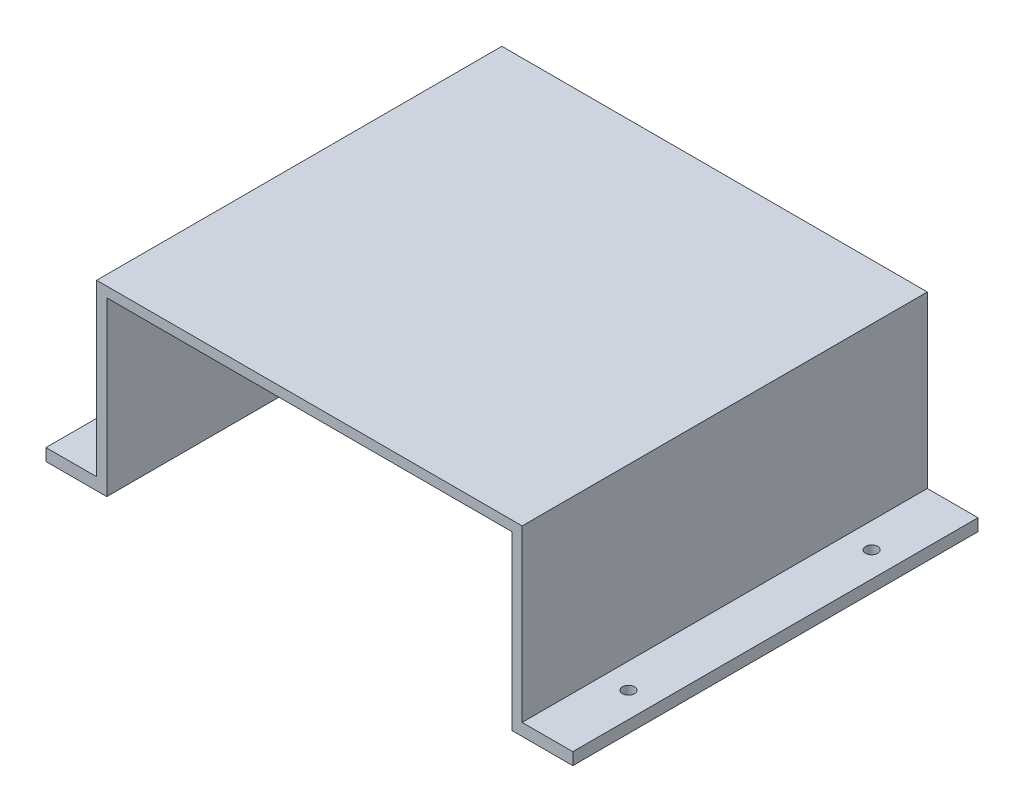
SolidWorks part; units mm, degrees
ref_plane "Front Plane" through (0, 0, 0) normal (0, 0, 1) x (1, 0, 0)
ref_plane "Top Plane" through (0, 0, 0) normal (0, 1, 0) x (1, 0, 0)
ref_plane "Right Plane" through (0, 0, 0) normal (1, 0, 0) x (0, 0, -1)
sketch "Sketch1" plane through (0, 0, 0) normal (0, 0, 1) x (1, 0, 0)
  line L1 (-67.9265, -4.0405) -> (32.0735, -4.0405)
  line L2 (-67.9265, -4.0405) -> (-67.9265, -74.0405)
  line L3 (-67.9265, -74.0405) -> (32.0735, -74.0405)
  line L4 (32.0735, -4.0405) -> (32.0735, -74.0405)
  line L5 (-70.4265, -1.5405) -> (34.5735, -1.5405)
  line L6 (-70.4265, -1.5405) -> (-70.4265, -76.5405)
  line L7 (-70.4265, -76.5405) -> (34.5735, -76.5405)
  line L8 (34.5735, -1.5405) -> (34.5735, -76.5405)
  dimension "D1" = 100
  dimension "D2" = 70
  dimension "D3" = 2.5
  dimension "D4" = 2.5
  dimension "D5" = 2.5
  dimension "D6" = 2.5
extrude "Boss-Extrude1" add sketch "Sketch1" along normal blind 100
extrude "Boss-Extrude2" add sketch "Sketch1<2>" along normal blind 3 contours L6 L7 L8 L5
sketch "Sketch1<2>" plane through (0, 0, 0) normal (0, 0, 1) x (1, 0, 0) same geometry as "Sketch1"
sketch "Sketch4" plane through (0, -1.5405, 0) normal (0, 1, 0) x (1, 0, 0)
  line L0 (-68.2059, -51.5) -> (-67.9265, -51.5)
  line L2 (-67.9265, -3) -> (32.3529, -3)
  line L3 (-67.9265, -3) -> (-67.9265, -51.5)
  line L5 (32.3529, -3) -> (32.3529, -51.5)
  arc A0 (32.3529, -51.5) -> (-68.2059, -51.5) centre (-17.9265, -51.5) ccw
extrude "Boss-Extrude3" add sketch "Sketch4" against normal blind 73 contours A0 L2 L3 | A0 L5 L2 region at (22.6295, -1.5405, 14.0826) region at (-58.2185, -1.5405, 13.7681)
sketch "Sketch5" plane through (0, -76.5405, 0) normal (0, -1, 0) x (1, 0, 0)
  line L1 (-67.9265, 100) -> (31.6349, 100)
  line L2 (-67.9265, 100) -> (-67.9265, 46.2067)
  line L3 (-31.579, 3.1096) -> (-4.2739, 3.1096)
  line L4 (31.6349, 100) -> (31.6349, 43.0327)
  arc A1 (-67.9265, 46.2067) -> (-31.1842, 3) centre (-17.9265, 51.5) ccw construction
  arc A2 (-4.6687, 3) -> (32.0735, 46.2067) centre (-17.9265, 51.5) ccw construction
  arc A3 (-67.9265, 46.2067) -> (-31.579, 3.1096) centre (-17.9265, 51.5) ccw
  arc A4 (-4.2739, 3.1096) -> (32.0735, 46.2067) centre (-17.9265, 51.5) ccw
  line M3 (34.5735, 100) -> (-70.4265, 100)
extrude "Cut-Extrude3" cut sketch "Sketch5" against normal blind 21.5 contours L3 A4 L4 L2 A3 M3 region at (-18.0648, -76.5405, 55.3892)
sketch "Sketch6" plane through (0, -76.5405, 0) normal (0, -1, 0) x (1, 0, 0)
  line L8 (-67.9265, 46.2067) -> (-67.9265, 100)
  line L9 (-67.9265, 100) -> (-70.4265, 100)
  line L10 (-70.4265, 100) -> (-70.4265, 0)
  line L11 (-70.4265, 0) -> (34.5735, 0)
  line L12 (34.5735, 0) -> (34.5735, 100)
  line L13 (34.5735, 100) -> (31.6349, 100)
  line L14 (31.6349, 100) -> (31.6349, 43.0327)
  line L15 (-4.2739, 3.1096) -> (-31.579, 3.1096)
  line L16 (-67.9265, 46.2067) -> (-67.9265, 100)
  line L17 (-67.9265, 100) -> (-70.4265, 100)
  line L18 (-70.4265, 100) -> (-70.4265, 0)
  line L19 (-70.4265, 0) -> (34.5735, 0)
  line L20 (34.5735, 0) -> (34.5735, 100)
  line L21 (34.5735, 100) -> (31.6349, 100)
  line L22 (31.6349, 100) -> (31.6349, 43.0327)
  line L23 (-4.2739, 3.1096) -> (-31.579, 3.1096)
  arc A2 (-67.9265, 46.2067) -> (-31.579, 3.1096) centre (-17.9265, 51.5) ccw
  arc A3 (-4.2739, 3.1096) -> (31.6349, 43.0327) centre (-17.9265, 51.5) ccw
  arc A4 (-67.9265, 46.2067) -> (-31.579, 3.1096) centre (-17.9265, 51.5) ccw
  arc A5 (-4.2739, 3.1096) -> (31.6349, 43.0327) centre (-17.9265, 51.5) ccw
  dimension "D1" = 0
extrude "Cut-Extrude4" cut sketch "Sketch6" against normal blind 30
sketch "Sketch7" plane through (0, 0, 3) normal (0, 0, 1) x (1, 0, 0)
  line L0 (-31.1842, -46.5405) -> (-31.1842, -4.0405) construction
  line L1 (-31.1842, -42.6279) -> (-4.6687, -42.6279)
  line L2 (-31.1842, -42.6279) -> (-31.1842, -4.0405)
  line L3 (-31.1842, -4.0405) -> (-4.6687, -4.0405)
  line L4 (-4.6687, -42.6279) -> (-4.6687, -4.0405)
  dimension "D1" = 38.5874
extrude "Cut-Extrude5" cut sketch "Sketch7" against normal blind 71 contours L2 L3 L4 L1
sketch "Sketch8" plane through (0, -46.5405, 0) normal (0, -1, 0) x (1, 0, 0)
  line L0 (47.0735, -3) -> (47.0735, 100) construction
  line L1 (-82.9265, 100) -> (47.0735, 100)
  line L2 (-82.9265, 100) -> (-82.9265, 0)
  line L3 (-82.9265, 0) -> (47.0735, 0)
  line L4 (47.0735, 100) -> (47.0735, 0)
  line L6 (-70.4265, 100) -> (34.5735, 100)
  line L7 (-70.4265, 100) -> (-70.4265, 0)
  line L8 (-70.4265, 0) -> (34.5735, 0)
  line L9 (34.5735, 100) -> (34.5735, 0)
  circle A0 centre (-76.6765, 80) radius 1.5
  circle A1 centre (-76.6765, 20) radius 1.5
  circle A2 centre (40.8235, 80) radius 1.5
  circle A3 centre (40.8235, 20) radius 1.5
  line M7 (-70.4265, 100) -> (-70.4265, 0)
  line M9 (34.5735, 0) -> (34.5735, 100)
  dimension "D1" = 3
  dimension "D2" = 3
  dimension "D6" = 60
  dimension "D3" = 60
  dimension "D4" = 20
  dimension "D5" = 6.25
  dimension "D7" = 6.25
extrude "Boss-Extrude4" add sketch "Sketch8" against normal blind 3 contours L2 L3 L1 A1 A0 M7 | L4 L1 L3 A3 A2 M9 region at (-76.6765, -46.5405, 50) region at (40.8235, -46.5405, 50)
sketch "Sketch9" plane through (0, 0, 0) normal (0, 0, -1) x (-1, 0, 0)
  circle A0 centre (-24.5735, -22.5405) radius 1.5
  circle A1 centre (60.4265, -22.5405) radius 1.5
extrude "Cut-Extrude6" cut sketch "Sketch9" against normal blind 6
